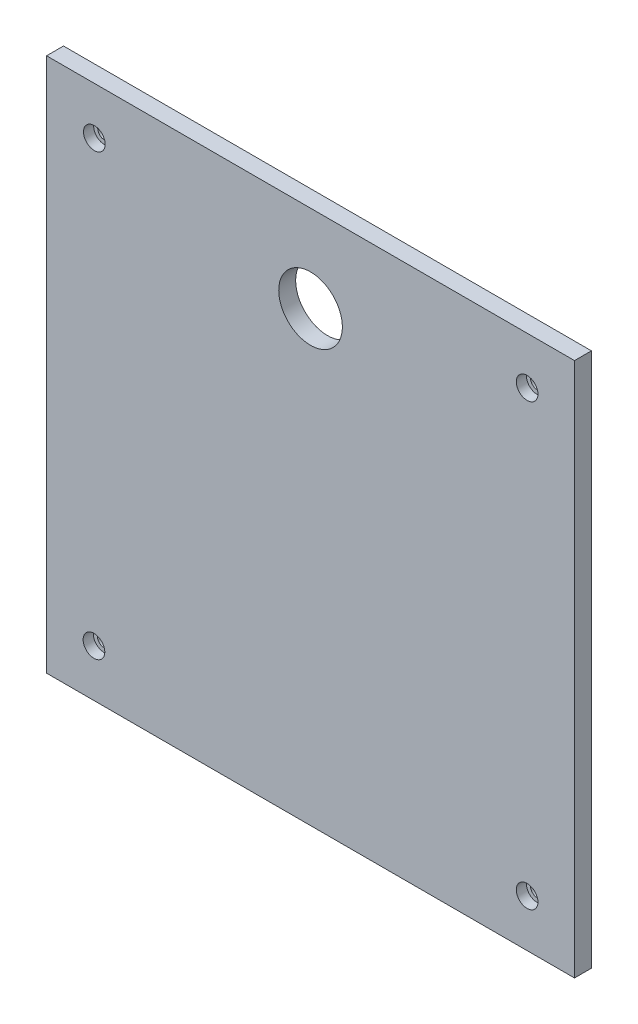
SolidWorks part; units mm, degrees
other "标注1"
sketch "草图10" plane through (-45.2426, 41.5897, 0) normal (-0.9994, 0.0059, 0.0328) x (0.0288, 0.6507, 0.7588)
ref_plane "前视基准面" through (0, 0, 0) normal (0, 0, 1) x (1, 0, 0)
ref_plane "上视基准面" through (0, 0, 0) normal (0, 1, 0) x (1, 0, 0)
ref_plane "右视基准面" through (0, 0, 0) normal (1, 0, 0) x (0, 0, -1)
sketch "外壳尺寸" plane through (0, 0, 0) normal (0, 0, 1) x (1, 0, 0)
  line L0 (-17.2361, -38.5079) -> (-14.2361, -38.5079)
  line L1 (38.764, -20.5078) -> (38.764, 15.4923)
  line L2 (-32.0459, 28.2943) -> (-38.764, 28.2943) construction
  line L3 (-32.0459, 13.1812) -> (-37.5195, 13.1812) construction
  line L4 (-33.9609, 7.4653) -> (-37.4846, 7.4653) construction
  line L5 (-33.9609, 0.9479) -> (-36.9615, 0.9479) construction
  line L6 (-34.7732, -15.6918) -> (-38.0077, -15.6918) construction
  line L7 (-34.7732, -21.1918) -> (-37.659, -21.1918) construction
  line L8 (-34.9146, -2.0109) -> (-36.6806, -2.0109) construction
  line L9 (-34.8191, -12.0127) -> (-36.3783, -12.0127) construction
  line L10 (16.4218, 37.9891) -> (16.4218, 33.2886) construction
  line L11 (28.422, 38.5079) -> (28.422, 33.6659) construction
  line L12 (-33.7426, -11.5127) -> (-35.165, -11.5127) construction
  line L13 (1.7639, 41.5897) -> (1.7639, -41.6804) construction
  line L14 (-35.165, -2.5109) -> (-33.7655, -2.5109) construction
  line L15 (45.0157, -1.0079) -> (-45.2426, -1.0079) construction
  line L16 (27.422, 35.861) -> (27.422, 36.7889) construction
  line L17 (17.4218, 35.861) -> (17.4218, 36.805) construction
  line L19 (-37.2361, -40.5079) -> (40.7639, -40.5079)
  line L20 (-37.2361, -40.5079) -> (-37.2361, 38.4921)
  line L21 (-37.2361, 38.4921) -> (40.7639, 38.4921)
  line L22 (40.7639, -40.5079) -> (40.7639, 38.4921)
  line L23 (-37.2361, -40.5079) -> (40.7639, 38.4921) construction
  line L24 (-37.2361, 38.4921) -> (40.7639, -40.5079) construction
  line L31 (-35.2362, -38.5079) -> (-17.2361, -38.5079)
  line L32 (-14.2361, -38.5079) -> (38.764, -38.5079)
  line L33 (38.764, -38.5079) -> (38.764, -20.5078)
  line L34 (38.764, 15.4923) -> (38.764, 36.4923)
  line L35 (38.764, 36.4923) -> (-35.2362, 36.4923)
  line L36 (-35.2362, 36.4923) -> (-35.2362, -38.5079)
  arc A2 (0.4641, 25.6357) -> (0.4641, 25.6425) centre (1.7641, 25.6391) ccw construction
  arc A3 (-2.2359, 25.6384) -> (-2.2359, 25.6425) centre (1.7643, 25.6405) ccw construction
  circle A5 centre (-30.1798, 31.4921) radius 1
  circle A6 centre (33.764, 31.4923) radius 1
  circle A7 centre (33.764, -33.5078) radius 1
  circle A8 centre (-30.2361, -33.5078) radius 1
  circle A9 centre (-30.1798, 31.4921) radius 1.6
  circle A10 centre (33.764, 31.4923) radius 1.6
  circle A11 centre (-30.2361, -33.5078) radius 1.6
  circle A12 centre (33.764, -33.5078) radius 1.6
  circle A13 centre (1.7641, 25.6391) radius 4.7
  point P51 (1.7639, -1.0079)
  point P52 (1.7639, -1.0079)
  dimension "D9" = 2
  dimension "D10" = 2
  dimension "D11" = 2
  dimension "D12" = 2
  dimension "D21" = 9.4
  dimension "D26" = 3.2
  dimension "D27" = 3.2
  dimension "D28" = 3.2
  dimension "D29" = 3.2
  dimension "D1" = 37.0001
  dimension "D2" = 37.5002
  dimension "D3" = 1
  dimension "D4" = 1
  dimension "D5" = 0.5
  dimension "D6" = 0.5
  dimension "D7" = 37.0001
  dimension "D8" = 37.5
  dimension "D13" = 5.0002
  dimension "D14" = 5.0564
  dimension "D15" = 5
  dimension "D16" = 5
  dimension "D17" = 5
  dimension "D18" = 5
  dimension "D19" = 5
  dimension "D20" = 5
  dimension "D24" = 78
  dimension "D25" = 79
extrude "凸台-拉伸3" add sketch "外壳尺寸" along normal blind 2.5 contours L21 L22 L19 L20
extrude "切除-拉伸4" cut sketch "外壳尺寸<10>" along normal up to next contours A5 | A8 | A7 | A6 | A13
sketch "外壳尺寸<10>" plane through (0, 0, 0) normal (0, 0, 1) x (1, 0, 0) same geometry as "外壳尺寸"
extrude "切除-拉伸6" cut sketch "外壳尺寸<12>" along normal blind 2.5 from offset 1 contours A9 | A10 | A12 | A11
sketch "外壳尺寸<12>" plane through (0, 0, 0) normal (0, 0, 1) x (1, 0, 0) same geometry as "外壳尺寸"
sketch "草图11" plane through (0, 0, 0) normal (0, 0, -1) x (-1, 0, 0)
  line L0 (-1.7639, 47.0859) -> (-1.7639, -45.1277) construction
  line L1 (-40.7639, -40.5079) -> (-40.7639, 38.4921) construction
  line L3 (42.0153, -1.0079) -> (-46.8656, -1.0079) construction
  line L7 (37.2361, 38.4921) -> (-40.7639, 38.4921) construction
  line L8 (29.2361, -33.5087) -> (29.1798, 31.4913) construction
  line L9 (-32.764, 31.4923) -> (-32.764, -33.5078) construction
  line L10 (-33.764, -32.5078) -> (30.2361, -32.5078) construction
  line L11 (-1.7641, 20.9391) -> (32.129, 20.9391) construction
  line L13 (27.2361, 19.4391) -> (-29.764, 19.4391)
  line L14 (27.2361, 19.4391) -> (27.2361, -29.5078)
  line L15 (27.2361, -29.5078) -> (-29.764, -29.5078)
  line L16 (-29.764, 19.4391) -> (-29.764, -29.5078)
  circle A0 centre (30.2361, -33.5078) radius 1 construction
  circle A1 centre (30.1798, 31.4921) radius 1 construction
  circle A2 centre (-33.764, 31.4923) radius 1 construction
  circle A3 centre (-33.764, -33.5078) radius 1 construction
  circle A4 centre (-1.7641, 25.6391) radius 4.7 construction
  dimension "D1" = 39
  dimension "D2" = 39.5
  dimension "D3" = 3
  dimension "D4" = 3
  dimension "D5" = 3
  dimension "D6" = 29
extrude "切除-拉伸7" cut sketch "草图11" against normal blind 1
